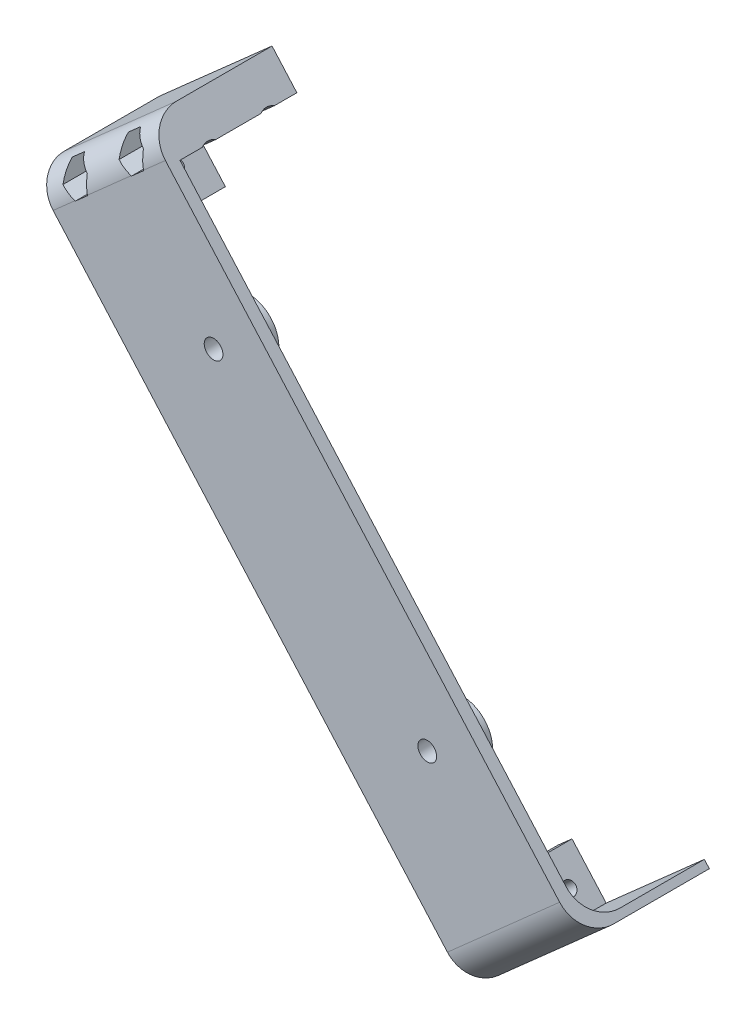
SolidWorks part; units mm, degrees
ref_plane "Front Plane" through (0, 0, 0) normal (0, 0, 1) x (1, 0, 0)
ref_plane "Top Plane" through (0, 0, 0) normal (0, 1, 0) x (1, 0, 0)
ref_plane "Right Plane" through (0, 0, 0) normal (1, 0, 0) x (0, 0, -1)
sketch "Sketch1" plane through (0, 0, 0) normal (0, 0, 1) x (1, 0, 0)
  circle A0 centre (0, 0) radius 10.2489
  circle A1 centre (-72.4111, 81.7658) radius 10.2489
extrude "Boss-Extrude1" add sketch "Sketch1" along normal up to surface (2.9845 mm away)
sketch "Sketch2" plane through (0, 0, 2.9845) normal (0, 0, 1) x (1, 0, 0)
  circle A0 centre (-72.4111, 81.7658) radius 10.2489
  circle A1 centre (0, 0) radius 10.2489
extrude "Boss-Extrude2" add sketch "Sketch2" along normal blind 5.08
sketch "Sketch3" plane through (0, 0, 8.0645) normal (0, 0, 1) x (1, 0, 0)
  line L0 (-134.0697, 103.5005) -> (-96.0391, 137.1801)
  line L1 (-134.0697, 103.5005) -> (14.1204, -63.8342)
  line L2 (-96.0391, 137.1801) -> (52.151, -30.1546)
  line L3 (14.1204, -63.8342) -> (52.151, -30.1546)
  line L4 (14.1204, -63.8342) -> (52.151, -30.1546) construction
  dimension "D1" = 0
extrude "Boss-Extrude3" add sketch "Sketch3" along normal blind 3.81
hole_wizard "1/4 (0.25) Diameter Hole1" positions "Sketch4" profile "Sketch5" hole size "1/4" standard "ANSI Inch" end condition through all
sketch "Sketch4" plane through (0, 0, 11.8745) normal (0, 0, 1) x (1, 0, 0)
  point P0 (0, 0)
  point P3 (-72.4111, 81.7658)
sketch "Sketch5" plane through (0, 0, 11.8745) normal (1, 0, 0) x (0, -1, 0)
  line L0 (0, 0) -> (0, 11.8745)
  line L1 (0, 11.8745) -> (3.175, 11.8745)
  line L2 (3.175, 11.8745) -> (3.175, 0)
  line L5 (3.175, 0) -> (0, 0)
  line L11 (0, -6.35) -> (0, 107.95) construction
  dimension "Thru Hole Dia." = 6.35
  dimension "Thru Hole Depth" = 11.8745
sketch "Sketch7" plane through (0, 0, 8.0645) normal (0, 0, -1) x (-1, 0, 0)
  line L0 (134.0697, 103.5005) -> (129.3159, 107.7104)
  line L1 (134.0697, 103.5005) -> (120.81, 88.5278)
  line L4 (96.0391, 137.1801) -> (134.0697, 103.5005) construction
  line L5 (61.8507, 31.5295) -> (66.6045, 27.3195)
  line L6 (69.7345, 24.5476) -> (46.6379, 45.0017)
  line L7 (61.8507, 31.5295) -> (48.591, 16.5568)
  line L8 (66.6045, 27.3195) -> (53.3448, 12.3468)
  line L9 (48.591, 16.5568) -> (53.3448, 12.3468)
  line L10 (129.3159, 107.7104) -> (96.0391, 137.1801)
  line L11 (134.0697, 103.5005) -> (-14.1204, -63.8342)
  line L12 (-5.6145, -44.6515) -> (-0.8607, -48.8615)
  line L13 (-5.6145, -44.6515) -> (-18.8742, -59.6242)
  line L14 (-0.8607, -48.8615) -> (-14.1204, -63.8342)
  line L15 (-18.8742, -59.6242) -> (-14.1204, -63.8342)
  line M7 (-14.1204, -63.8342) -> (134.0697, 103.5005)
  line M10 (-52.151, -30.1546) -> (-14.1204, -63.8342)
  dimension "D3" = 20
  dimension "D4" = 0
  dimension "D5" = 101.76
  dimension "D6" = 0
  dimension "D7" = 6.35
extrude "Boss-Extrude4" add sketch "Sketch7" along normal blind 17.78 contours L7 L9 L5 M7 | L12 L13 M10 M7 region at (9.8675, -54.2428, 8.0645) region at (-57.5977, 21.9381, 8.0645)
sketch "Sketch8" plane through (-19.0153, -16.8398, 0) normal (0.7486, 0.663, 0) x (0, 0, -1)
  circle A0 centre (4.6355, -47.15) radius 2.25
  circle A1 centre (0, 54.61) radius 2.25
  dimension "D1" = 4.5
extrude "Cut-Extrude1" cut sketch "Sketch8" against normal blind 17.78
sketch "Sketch9" plane through (-19.0153, -16.8398, 0) normal (0.7486, 0.663, 0) x (0, 0, -1)
  line L0 (9.7155, -57.15) -> (-8.0645, -57.15)
  line L1 (9.7155, -57.15) -> (9.7155, -54.61)
  line L2 (-8.0645, -57.15) -> (-8.0645, -54.61)
  line L3 (9.7155, -54.61) -> (-8.0645, -54.61)
  line L4 (9.7155, 44.61) -> (-8.0645, 44.61)
  line L5 (9.7155, 44.61) -> (9.7155, 47.15)
  line L6 (-8.0645, 44.61) -> (-8.0645, 47.15)
  line L7 (9.7155, 47.15) -> (-8.0645, 47.15)
  line L8 (9.7155, 64.61) -> (-8.0645, 64.61)
  line L9 (9.7155, 64.61) -> (9.7155, 62.07)
  line L10 (-8.0645, 64.61) -> (-8.0645, 62.07)
  line L11 (9.7155, 62.07) -> (-8.0645, 62.07)
  line L12 (9.7155, -37.15) -> (-8.0645, -37.15)
  line L13 (9.7155, -37.15) -> (9.7155, -39.69)
  line L14 (-8.0645, -37.15) -> (-8.0645, -39.69)
  line L15 (9.7155, -39.69) -> (-8.0645, -39.69)
extrude "Boss-Extrude5" add sketch "Sketch9" along normal blind 17.78
sketch "Sketch10" plane through (37.8895, -42.7844, 0) normal (0.663, -0.7486, 0) x (0.7486, 0.663, 0)
  line L0 (-7.62, 8.0645) -> (-7.62, -9.7155)
  line L2 (-7.62, -9.7155) -> (-25.4, -9.7155)
  line L4 (-25.4, -9.7155) -> (-7.62, 8.0645)
extrude "Cut-Extrude2" cut sketch "Sketch10" against normal up to surface (20 mm away) up to face at (9.893, -40.8626, -0.8255)
sketch "Sketch11" plane through (-29.5757, 33.3966, 0) normal (0.663, -0.7486, 0) x (0.7486, 0.663, 0)
  line L0 (-7.62, -9.7155) -> (-7.62, 8.0645)
  line L1 (-7.62, -9.7155) -> (-25.4, -9.7155)
  line L4 (-25.4, -9.7155) -> (-7.62, 8.0645)
extrude "Cut-Extrude3" cut sketch "Sketch11" against normal up to surface (20 mm away) up to face at (-57.5722, 35.3184, -0.8255)
sketch "Sketch12" plane through (37.8895, -42.7844, 0) normal (0.663, -0.7486, 0) x (0.7486, 0.663, 0)
  line L0 (-25.4, -9.7155) -> (19.05, -9.7155)
  line L1 (19.05, -9.7155) -> (19.05, 8.0645)
  line L2 (19.05, 8.0645) -> (-7.62, 8.0645)
  line L3 (-7.62, 8.0645) -> (-25.4, -9.7155)
extrude "Boss-Extrude6" add sketch "Sketch12" against normal up to surface (2.54 mm away) up to face at (21.6271, -53.7934, 2.1378)
sketch "Sketch13" plane through (0, 0, 8.0645) normal (0, 0, -1) x (-1, 0, 0)
  line L0 (96.0391, 137.1801) -> (134.0697, 103.5005)
  line L1 (96.0391, 137.1801) -> (87.6192, 127.6724)
  line L2 (134.0697, 103.5005) -> (125.6498, 93.9928)
  line L3 (87.6192, 127.6724) -> (125.6498, 93.9928)
  line L4 (134.0697, 103.5005) -> (66.6045, 27.3195) construction
  line L5 (96.0391, 137.1801) -> (134.0697, 103.5005) construction
  dimension "D1" = 12.7
  dimension "D2" = 50.8
extrude "Boss-Extrude7" add sketch "Sketch13" along normal blind 39.624
sketch "Sketch14" plane through (0, 0, 11.8745) normal (0, 0, 1) x (1, 0, 0)
  line L0 (-134.0697, 103.5005) -> (-96.0391, 137.1801)
  line L1 (-134.0697, 103.5005) -> (-125.6498, 93.9928)
  line L2 (-96.0391, 137.1801) -> (-87.6192, 127.6724)
  line L3 (-125.6498, 93.9928) -> (-87.6192, 127.6724)
  line L4 (-96.0391, 137.1801) -> (-134.0697, 103.5005) construction
  line L5 (-106.6345, 110.8326) -> (-115.0544, 120.3403)
  line L6 (-110.8445, 115.5865) -> (-91.8292, 132.4262)
  line L7 (-110.8445, 115.5865) -> (-129.8598, 98.7467)
  line L9 (-116.2352, 110.8125) -> (-121.4511, 112.5549)
  line L10 (-121.4511, 112.5549) -> (-125.568, 108.909)
  line L11 (-125.568, 108.909) -> (-124.469, 103.5206)
  line L12 (-124.469, 103.5206) -> (-119.2531, 101.7782)
  line L13 (-119.2531, 101.7782) -> (-115.1362, 105.4242)
  line L14 (-115.1362, 105.4242) -> (-116.2352, 110.8125)
  line L15 (-97.2199, 127.6523) -> (-102.4358, 129.3947)
  line L16 (-102.4358, 129.3947) -> (-106.5527, 125.7488)
  line L17 (-106.5527, 125.7488) -> (-105.4537, 120.3604)
  line L18 (-105.4537, 120.3604) -> (-100.2378, 118.618)
  line L19 (-100.2378, 118.618) -> (-96.1209, 122.2639)
  line L20 (-96.1209, 122.2639) -> (-97.2199, 127.6523)
  circle A0 centre (-120.3521, 107.1666) radius 4.7625 construction
  circle A1 centre (-101.3368, 124.0063) radius 4.7625 construction
  point P11 (-120.3521, 107.1666)
  point P12 (-101.3368, 124.0063)
  dimension "D1" = 12.7
  dimension "D2" = 9.525
  dimension "D3" = 9.525
hole_wizard "#6 Clearance Hole1" positions "Sketch15" profile "Sketch16" hole size "#6" standard "ANSI Inch" end condition through all
sketch "Sketch15" plane through (0, 0, 11.8745) normal (0, 0, 1) x (1, 0, 0)
  point P0 (-120.3521, 107.1666)
  point P2 (-101.3368, 124.0063)
sketch "Sketch16" plane through (-120.3521, 107.1666, 11.8745) normal (1, 0, 0) x (0, -1, 0)
  line L0 (0, 0) -> (0, 43.434)
  line L1 (0, 43.434) -> (1.8986, 43.434)
  line L2 (1.8986, 43.434) -> (1.8986, 0)
  line L5 (1.8986, 0) -> (0, 0)
  line L11 (0, -6.35) -> (0, 107.95) construction
  dimension "Thru Hole Dia." = 3.7973
  dimension "Thru Hole Depth" = 43.434
extrude "Cut-Extrude4" cut sketch "Sketch14" against normal blind 6.35 contours L16 L17 L6 L15 | L19 L20 L6 L18 | L10 L11 L7 L9 | L13 L14 L7 L12 region at (-121.7554, 108.7512, 11.8745) region at (-118.9488, 105.582, 11.8745) region at (-102.7401, 125.591, 11.8745) region at (-99.9335, 122.4217, 11.8745)
sketch "Sketch17" plane through (-23.7691, -21.0497, 0) normal (-0.7486, -0.663, 0) x (0, 0, 1)
  line L0 (8.0645, 140.02) -> (8.0645, 160.02)
  line L1 (8.0645, 140.02) -> (-31.5595, 140.02)
  line L2 (8.0645, 160.02) -> (-31.5595, 160.02)
  line L3 (-31.5595, 140.02) -> (-31.5595, 160.02)
  line L4 (8.0645, -54.61) -> (8.0645, 153.67) construction
  line L5 (-31.5595, 166.37) -> (-31.5595, 153.67) construction
  dimension "D1" = 20
  dimension "D2" = 0
extrude "Boss-Extrude8" add sketch "Sketch17" against normal blind 6.35
sketch "Sketch18" plane through (-19.0153, -16.8398, 0) normal (0.7486, 0.663, 0) x (0, 0, -1)
  line L0 (-8.0645, 140.02) -> (31.5595, 140.02)
  line L1 (-8.0645, 140.02) -> (-8.0645, 160.02)
  line L2 (31.5595, 140.02) -> (31.5595, 160.02)
  line L3 (-8.0645, 160.02) -> (31.5595, 160.02)
  line L4 (11.7475, 140.02) -> (11.7475, 160.02)
  line L5 (-8.0645, 150.02) -> (11.7475, 150.02)
  line L6 (11.7475, 150.02) -> (31.5595, 150.02)
  point P11 (1.8415, 150.02)
  point P12 (21.6535, 150.02)
  dimension "D1" = 20
hole_wizard "M4 Clearance Hole1" positions "Sketch19" profile "Sketch20" hole size "M4" standard "ANSI Metric" end condition through all
sketch "Sketch19" plane through (-19.0153, -16.8398, 0) normal (0.7486, 0.663, 0) x (0, 0, -1)
  line L0 (11.7475, 150.02) -> (31.5595, 150.02) construction
  point P0 (1.8415, 150.02)
  point P3 (21.6535, 150.02)
sketch "Sketch20" plane through (-118.4761, 95.4703, -1.8415) normal (0, 0, 1) x (-0.663, 0.7486, 0)
  line L0 (0, 0) -> (0, 117.2901)
  line L1 (0, 117.2901) -> (2.25, 117.2901)
  line L2 (2.25, 117.2901) -> (2.25, 0)
  line L5 (2.25, 0) -> (0, 0)
  line L11 (0, -6.35) -> (0, 107.95) construction
  dimension "Thru Hole Dia." = 4.5
  dimension "Thru Hole Depth" = 117.2901
sketch "Sketch21" plane through (-19.0153, -16.8398, 0) normal (0.7486, 0.663, 0) x (0, 0, -1)
  circle A2 centre (21.6535, 150.02) radius 4.308
  circle A3 centre (1.8415, 150.02) radius 4.308
extrude "Cut-Extrude5" cut sketch "Sketch21" along normal through all
fillet "Fillet2" radius 11 3 edges at (33.8286, -42.9879, 8.0645) (33.1357, -46.9944, 11.8745) (-115.0544, 120.3403, 11.8745)
sketch "Sketch22" plane through (0, 0, 5.5245) normal (0, 0, 1) x (1, 0, 0)
  line L0 (-121.4511, 112.5549) -> (-125.568, 108.909) construction
  line L1 (-125.568, 108.909) -> (-124.469, 103.5206) construction
  line L2 (-124.469, 103.5206) -> (-119.2531, 101.7782) construction
  line L3 (-119.2531, 101.7782) -> (-115.1362, 105.4242) construction
  line L4 (-115.1362, 105.4242) -> (-116.2352, 110.8125) construction
  line L5 (-116.2352, 110.8125) -> (-121.4511, 112.5549) construction
  line L6 (-102.4358, 129.3947) -> (-106.5527, 125.7488) construction
  line L7 (-106.5527, 125.7488) -> (-105.4537, 120.3604) construction
  line L8 (-105.4537, 120.3604) -> (-100.2378, 118.618) construction
  line L9 (-100.2378, 118.618) -> (-96.1209, 122.2639) construction
  line L10 (-96.1209, 122.2639) -> (-97.2199, 127.6523) construction
  line L11 (-97.2199, 127.6523) -> (-102.4358, 129.3947) construction
  line L12 (-121.4511, 112.5549) -> (-125.568, 108.909)
  line L13 (-125.568, 108.909) -> (-124.469, 103.5206)
  line L14 (-124.469, 103.5206) -> (-119.2531, 101.7782)
  line L15 (-119.2531, 101.7782) -> (-115.1362, 105.4242)
  line L16 (-115.1362, 105.4242) -> (-116.2352, 110.8125)
  line L17 (-116.2352, 110.8125) -> (-121.4511, 112.5549)
  line L18 (-102.4358, 129.3947) -> (-106.5527, 125.7488)
  line L19 (-106.5527, 125.7488) -> (-105.4537, 120.3604)
  line L20 (-105.4537, 120.3604) -> (-100.2378, 118.618)
  line L21 (-100.2378, 118.618) -> (-96.1209, 122.2639)
  line L22 (-96.1209, 122.2639) -> (-97.2199, 127.6523)
  line L23 (-97.2199, 127.6523) -> (-102.4358, 129.3947)
extrude "Cut-Extrude6" cut sketch "Sketch22" against normal blind 6.35
ref_plane "Plane1" through (-87.6192, 127.6724, 8.0645) normal (-0.663, 0.7486, 0) x (0.7486, 0.663, 0)
sketch "Sketch24" plane through (0, 0, -9.7155) normal (0, 0, -1) x (-1, 0, 0)
  line L7 (-7.2985, -46.5531) -> (-17.1902, -57.7227)
  line L8 (-17.1902, -57.7227) -> (-50.467, -28.2531)
  line L9 (-50.467, -28.2531) -> (-52.151, -30.1546)
  line L10 (-52.151, -30.1546) -> (-14.1204, -63.8342)
  line L11 (-14.1204, -63.8342) -> (-0.8607, -48.8615)
  line L12 (-0.8607, -48.8615) -> (-5.6145, -44.6515)
  line L13 (-5.6145, -44.6515) -> (-7.2985, -46.5531)
  line L14 (-7.2985, -46.5531) -> (-17.1902, -57.7227)
  line L15 (-17.1902, -57.7227) -> (-50.467, -28.2531)
  line L16 (-50.467, -28.2531) -> (-52.151, -30.1546)
  line L17 (-52.151, -30.1546) -> (-14.1204, -63.8342)
  line L18 (-14.1204, -63.8342) -> (-0.8607, -48.8615)
  line L19 (-0.8607, -48.8615) -> (-5.6145, -44.6515)
  line L20 (-5.6145, -44.6515) -> (-7.2985, -46.5531)
  dimension "D1" = 0
extrude "Boss-Extrude9" add sketch "Sketch24" along normal up to surface (21.844 mm away) up to face at (-111.1784, 106.3856, -31.5595)
sketch "Sketch25" plane through (-19.0153, -16.8398, 0) normal (0.7486, 0.663, 0) x (0, 0, -1)
  line L0 (23.9035, 150.02) -> (23.9035, -47.15)
  line L1 (4.6355, -47.15) -> (23.9035, -47.15)
  circle A0 centre (21.6535, 150.02) radius 2.25 construction
  circle A1 centre (23.9035, -47.15) radius 2.25
  circle A2 centre (4.6355, -47.15) radius 2.25 construction
  circle A3 centre (4.6355, -47.15) radius 2.25
  point P5 (23.9035, -47.15)
extrude "Cut-Extrude7" cut sketch "Sketch25" against normal through all contours L1 A1 L0 | L0 A1 L1 region at (12.4554, -52.3762, -24.2218) region at (11.6113, -51.423, -22.9486)
